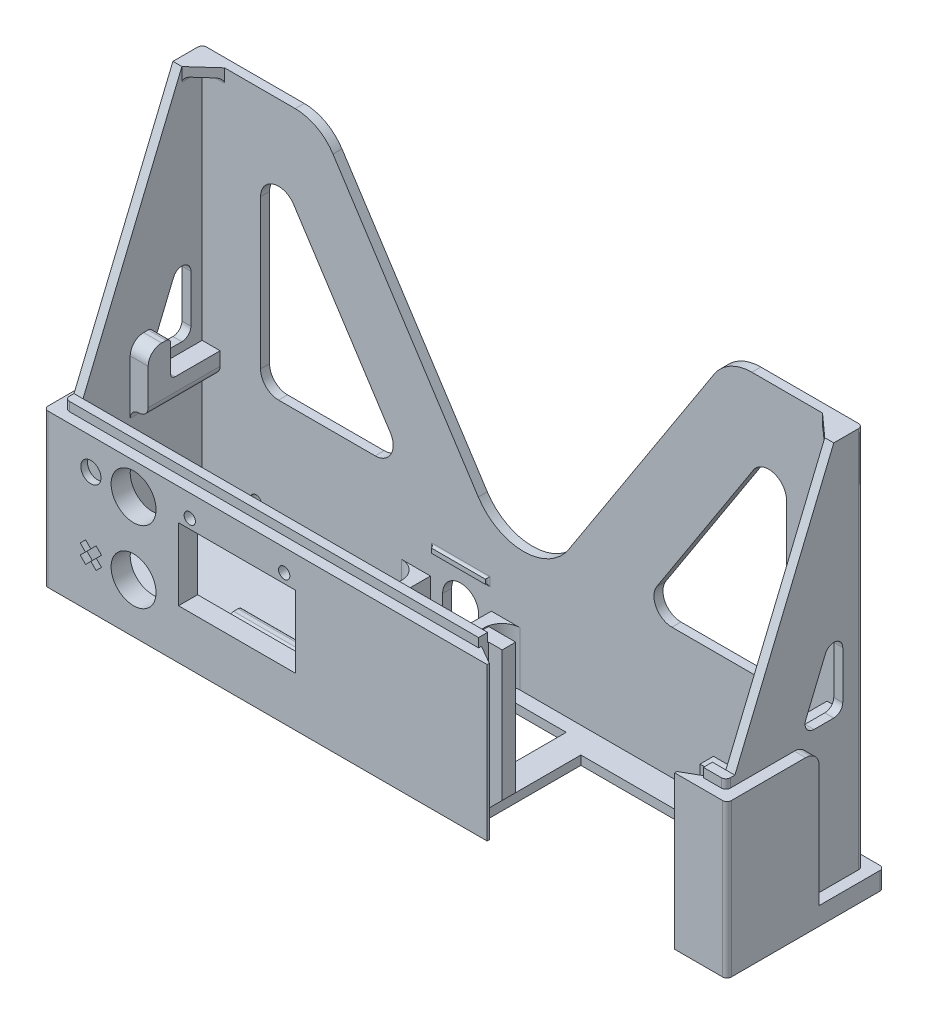
SolidWorks part; units mm, degrees
ref_plane "Plano frontal" through (0, 0, 0) normal (0, 0, 1) x (1, 0, 0)
ref_plane "Plano superior" through (0, 0, 0) normal (0, 1, 0) x (1, 0, 0)
ref_plane "Plano direito" through (0, 0, 0) normal (1, 0, 0) x (0, 0, -1)
sketch "Esboço1" plane through (0, 0, 0) normal (0, 1, 0) x (1, 0, 0)
  line L1 (0, 0) -> (152, 0)
  line L2 (0, 0) -> (0, 35)
  line L3 (0, 35) -> (152, 35)
  line L4 (152, 0) -> (152, 35)
extrude "Ressalto-extrusão1" add sketch "Esboço1" along normal blind 2
sketch "Esboço3" plane through (0, 2, 0) normal (0, 1, 0) x (1, 0, 0)
  line L0 (4, 31) -> (4, 4)
  line L1 (4, 4) -> (148, 4)
  line L2 (148, 4) -> (148, 31)
  line L3 (148, 31) -> (4, 31)
  line L8 (0, 35) -> (0, 0)
  line L9 (0, 0) -> (152, 0)
  line L10 (152, 0) -> (152, 35)
  line L11 (152, 35) -> (0, 35)
  line L12 (0, 35) -> (0, 0)
  line L13 (0, 0) -> (152, 0)
  line L14 (152, 0) -> (152, 35)
  line L15 (152, 35) -> (0, 35)
  dimension "D1" = 0
  dimension "D2" = 4
extrude "Ressalto-extrusão2" add sketch "Esboço3" along normal blind 32
sketch "Esboço5" plane through (0, 34, 0) normal (0, 1, 0) x (1, 0, 0)
  line L0 (152, 0) -> (152, 35) construction
  line L1 (0, 35) -> (152, 35)
  line L2 (0, 35) -> (0, 20.5)
  line L3 (0, 20.5) -> (152, 20.5)
  line L4 (152, 35) -> (152, 20.5)
  dimension "D1" = 14.5
extrude "Corte-extrusão1" cut sketch "Esboço5" against normal blind 30
fillet "Filete2" radius 3 2 edges at (2, 34, -20.5) (150, 34, -20.5)
sketch "Esboço6" plane through (0, 2, 0) normal (0, 1, 0) x (1, 0, 0)
  line L0 (152, 35) -> (0, 0) construction
  line L1 (0, 35) -> (152, 0) construction
  line L3 (149.5, 2.25) -> (2.5, 2.25)
  line L4 (149.5, 2.25) -> (149.5, 32.75)
  line L5 (149.5, 32.75) -> (2.5, 32.75)
  line L6 (2.5, 2.25) -> (2.5, 32.75)
  line L7 (149.5, 2.25) -> (2.5, 32.75) construction
  line L8 (149.5, 32.75) -> (2.5, 2.25) construction
  line L13 (147.5, 4.25) -> (4.5, 4.25)
  line L14 (4.5, 4.25) -> (4.5, 30.75)
  line L15 (147.5, 30.75) -> (4.5, 30.75)
  line L16 (147.5, 4.25) -> (147.5, 30.75)
  point P8 (76, 17.5)
  dimension "D1" = 147
  dimension "D2" = 30.5
  dimension "D3" = 2
extrude "Ressalto-extrusão3" add sketch "Esboço6" along normal offset from surface (87 mm away) 55 up to face at (76, 34, -9.75) offset beyond the face yes
fillet "Filete3" radius 1 8 edges at (2.5, 61.5, -2.25) (149.5, 61.5, -2.25) (149.5, 46.5, -32.75) (152, 2, -35) (0, 2, -35) (2.5, 46.5, -32.75) (152, 17, 0) (0, 17, 0)
sketch "Esboço7" plane through (0, 0, 0) normal (0, 0, 1) x (1, 0, 0)
  line L0 (1, 34) -> (151, 34) construction
  line L1 (30, 27) -> (56, 27)
  line L2 (30, 27) -> (30, 11)
  line L3 (30, 11) -> (56, 11)
  line L4 (56, 27) -> (56, 11)
  line L5 (32.5, 29.1) -> (53.5, 29.1) construction
  line L6 (30, 27) -> (20, 27) construction
  line L7 (20, 27) -> (20, 11) construction
  line L9 (0, 4) -> (0, 31) construction
  circle A0 centre (20, 27) radius 5
  circle A1 centre (20, 11) radius 5
  circle A2 centre (32.5, 29.1) radius 1.25
  circle A3 centre (53.5, 29.1) radius 1.25
  dimension "D5" = 10
  dimension "D6" = 10
  dimension "D7" = 20
  dimension "D8" = 2.5
  dimension "D12" = 2.5
  dimension "D13" = 2.5
  dimension "D1" = 16
  dimension "D2" = 26
  dimension "D3" = 7
  dimension "D4" = 10
  dimension "D9" = 2.1
  dimension "D10" = 16
  dimension "D11" = 2.5
extrude "Corte-extrusão2" cut sketch "Esboço7" against normal up to surface (4.25 mm away) up to face at (76, 45.5, -4.25)
sketch "Esboço8" plane through (0, 0, 0) normal (0, 0, 1) x (1, 0, 0)
  line L0 (15, 11) -> (10.5, 11) construction
  line L1 (9.3333, 13.3688) -> (10.5, 12.2021)
  line L2 (8, 8.5) -> (13, 8.5) construction
  line L3 (8, 8.5) -> (8, 13.5) construction
  line L4 (8, 13.5) -> (13, 13.5) construction
  line L5 (13, 8.5) -> (13, 13.5) construction
  line L6 (8, 8.5) -> (13, 13.5) construction
  line L7 (8, 13.5) -> (13, 8.5) construction
  line L8 (9.3333, 13.3688) -> (8.1312, 12.1667)
  line L9 (12.8688, 9.8333) -> (11.6667, 8.6312)
  line L10 (8.1312, 12.1667) -> (9.2979, 11)
  line L11 (9.3333, 13.3688) -> (11.6667, 8.6312) construction
  line L12 (12.8688, 9.8333) -> (8.1312, 12.1667) construction
  line L13 (12.8688, 12.1667) -> (11.7021, 11)
  line L14 (12.8688, 12.1667) -> (11.6667, 13.3688)
  line L15 (9.3333, 8.6312) -> (8.1312, 9.8333)
  line L16 (11.6667, 13.3688) -> (10.5, 12.2021)
  line L17 (12.8688, 12.1667) -> (8.1312, 9.8333) construction
  line L18 (9.3333, 8.6312) -> (11.6667, 13.3688) construction
  line L19 (10.5, 9.7979) -> (11.6667, 8.6312)
  line L20 (10.5, 9.7979) -> (9.3333, 8.6312)
  line L21 (11.7021, 11) -> (12.8688, 9.8333)
  line L22 (9.2979, 11) -> (8.1312, 9.8333)
  line L23 (15, 27) -> (10.5, 27) construction
  circle A0 centre (10.5, 11) radius 2.5 construction
  circle A1 centre (20, 11) radius 5 construction
  circle A2 centre (20, 27) radius 5 construction
  circle A3 centre (10.5, 27) radius 2.25
  dimension "D1" = 5
  dimension "D3" = 4.5
  dimension "D2" = 4.5
  dimension "D4" = 4.5
extrude "Corte-extrusão3" cut sketch "Esboço8" against normal blind 1.5
sketch "Esboço10" plane through (0, 0, 0) normal (0, -1, 0) x (1, 0, 0)
  line L0 (1, 0) -> (151, 0) construction
  line L1 (139.5, 0) -> (99.5, 0)
  line L2 (144.5, -2.8868) -> (144.5, -25)
  line L3 (144.5, -25) -> (94.5, -25)
  line L4 (94.5, -2.8868) -> (94.5, -25)
  line L5 (151, -35) -> (1, -35) construction
  line L6 (147.5, -4.25) -> (147.5, -30.75) construction
  line L7 (98.634, -0.5) -> (94.5, -2.8868)
  line L8 (144.5, -2.8868) -> (140.366, -0.5)
  line L9 (99.5, 0) -> (98.634, 0)
  line L10 (98.634, 0) -> (98.634, -0.5)
  line L11 (139.5, 0) -> (140.366, 0)
  line L12 (140.366, 0) -> (140.366, -0.5)
  line L13 (99.5, 0) -> (98.634, -0.5) construction
  line L14 (140.366, -0.5) -> (139.5, 0) construction
  point P0 (144.5, 0)
  point P3 (94.5, 0)
  dimension "D1" = 10
  dimension "D2" = 3
  dimension "D3" = 50
  dimension "D4" = 5
  dimension "D5" = 30
  dimension "D6" = 5
  dimension "D7" = 30
  dimension "D8" = 0.5
  dimension "D9" = 0.5
extrude "Corte-extrusão5" cut sketch "Esboço10" against normal up to surface (89 mm away)
sketch "Esboço11" plane through (0, 89, 0) normal (0, 1, 0) x (1, 0, 0)
  line L0 (94.5, 2.8868) -> (94.5, 2.25)
  line L1 (3.5, 2.25) -> (95.6029, 2.25) construction
  line L2 (94.5, 2.25) -> (95.6029, 2.25)
  line L3 (95.6029, 2.25) -> (94.5, 2.8868)
  line L4 (143.3971, 2.25) -> (144.5, 2.8868)
  line L5 (144.5, 2.8868) -> (144.5, 2.25)
  line L6 (143.3971, 2.25) -> (148.5, 2.25) construction
  line L7 (144.5, 2.25) -> (143.3971, 2.25)
extrude "Corte-extrusão6" cut sketch "Esboço11" against normal up to surface (55 mm away) up to face at (147.4493, 34, -4.8706)
sketch "Esboço12" plane through (0, 0, 0) normal (0, -1, 0) x (1, 0, 0)
  line L0 (94.5, -2.8868) -> (94.5, -25) construction
  line L1 (74.5, -8.25) -> (88.5, -8.25)
  line L2 (74.5, -8.25) -> (74.5, -27.75)
  line L3 (74.5, -27.75) -> (88.5, -27.75)
  line L4 (88.5, -8.25) -> (88.5, -27.75)
  line L6 (56, -12.25) -> (68, -17.25) construction
  line L8 (56, -17.25) -> (56, -12.25)
  line L10 (68, -17.25) -> (68, -12.25)
  line L11 (68, -12.25) -> (56, -17.25) construction
  line L12 (62, -14.75) -> (74.5, -14.75) construction
  line L13 (4.5, -4.25) -> (94.5, -4.25) construction
  line L14 (74.5, -8.25) -> (62, -8.25) construction
  line L32 (62, -14.75) -> (62, -32) construction
  line L33 (151, -35) -> (1, -35) construction
  line L35 (58, -29) -> (66, -29)
  line L36 (58, -29) -> (58, -35)
  line L37 (58, -35) -> (66, -35)
  line L38 (66, -29) -> (66, -35)
  line L39 (58, -29) -> (66, -35) construction
  line L40 (58, -35) -> (66, -29) construction
  arc A0 (56, -17.25) -> (68, -17.25) centre (62, -14.75) ccw
  arc A1 (68, -12.25) -> (56, -12.25) centre (62, -14.75) ccw
  circle A2 centre (62, -14.75) radius 6.5 construction
  dimension "D4" = 6.5
  dimension "D6" = 12.5
  dimension "D1" = 14
  dimension "D2" = 19.5
  dimension "D3" = 6
  dimension "D5" = 12
  dimension "D7" = 4
  dimension "D11" = 6
  dimension "D17" = 8
extrude "Corte-extrusão7" cut sketch "Esboço12" against normal blind 16
fillet "Filete4" radius 4 4 edges at (62, 16, -30.75) (66, 16, -31.75) (58, 16, -31.75) (62, 16, -32.75)
sketch "Esboço15" plane through (0, 2, 0) normal (0, 1, 0) x (1, 0, 0)
  line L0 (68.6192, 22.35) -> (67.1192, 23.85)
  line L1 (68.8233, 24.75) -> (67.1192, 24.75)
  line L2 (68.8233, 24.75) -> (68.8233, 30.75)
  line L4 (55.2871, 24.75) -> (55.2871, 30.75)
  line L5 (68.8233, 24.75) -> (55.2871, 30.75) construction
  line L6 (68.8233, 30.75) -> (55.2871, 24.75) construction
  line L7 (147.5, 30.75) -> (4.5, 30.75) construction
  line L8 (52.8871, 22.35) -> (52.8871, 26.75)
  line L9 (71.2233, 22.35) -> (68.6192, 22.35)
  line L10 (71.2233, 22.35) -> (71.2233, 26.75)
  line L11 (56.9912, 24.75) -> (55.2871, 24.75)
  line L12 (55.4912, 22.35) -> (52.8871, 22.35)
  line L14 (67.1192, 24.75) -> (67.1192, 23.85)
  line L16 (56.9912, 24.75) -> (56.9912, 23.85)
  line L17 (68.8233, 24.75) -> (55.2871, 24.75) construction
  line L18 (71.2233, 30.75) -> (68.8233, 30.75)
  line L19 (71.2233, 22.35) -> (52.8871, 22.35) construction
  line L20 (55.2871, 30.75) -> (52.8871, 30.75)
  line L21 (56.9912, 23.85) -> (55.4912, 22.35)
  line L22 (52.8871, 30.75) -> (48.8871, 30.75)
  line L24 (71.2233, 22.35) -> (71.2233, 30.75) construction
  line L25 (71.2233, 30.75) -> (75.2233, 30.75)
  line L27 (52.8871, 22.35) -> (52.8871, 30.75) construction
  arc A0 (71.2233, 26.75) -> (75.2233, 30.75) centre (75.2233, 26.75) cw
  arc A1 (48.8871, 30.75) -> (52.8871, 26.75) centre (48.8871, 26.75) cw
  point P0 (62.0552, 27.75)
  point P13 (62.0552, 23.55)
  point P14 (56.9912, 22.35)
  point P16 (67.1192, 22.35)
  dimension "D3" = 1.5
  dimension "D6" = 4
  dimension "D7" = 4
  dimension "D1" = 1.5
  dimension "D2" = 2.4
  dimension "D4" = 1.5
  dimension "D5" = 1.5
extrude "Ressalto-extrusão4" add sketch "Esboço15" along normal blind 12
sketch "Esboço16" plane through (0, 0, -30.75) normal (0, 0, 1) x (1, 0, 0)
  line L0 (62, 2) -> (62, 19.5) construction
  line L1 (66, 2) -> (58, 2) construction
  line L3 (68, 20) -> (56, 20)
  line L4 (68, 20) -> (68, 19)
  line L5 (68, 19) -> (56, 19)
  line L6 (56, 20) -> (56, 19)
  line L7 (68, 20) -> (56, 19) construction
  line L8 (68, 19) -> (56, 20) construction
  dimension "D1" = 17
  dimension "D2" = 1
  dimension "D3" = 12
extrude "Ressalto-extrusão5" add sketch "Esboço16" along normal blind 0.5
fillet "Filete7" radius 0.5 4 edges at (56, 19.5, -30.75) (68, 19.5, -30.75) (62, 20, -30.75) (62, 19, -30.75)
sketch "Esboço18" plane through (30, 0, 0) normal (1, 0, 0) x (0, 0, -1)
  line L0 (4.25, 3.8) -> (7.25, 3.8)
  line L1 (4.25, 89) -> (4.25, 2) construction
  line L2 (8.25, 4.8) -> (8.25, 5.8)
  line L3 (9.25, 6.8) -> (10.25, 6.8)
  line L9 (11.25, 5.8) -> (11.25, 2)
  line L10 (30.75, 2) -> (4.25, 2) construction
  line L11 (11.25, 2) -> (4.25, 2)
  line L12 (4.25, 2) -> (4.25, 3.8)
  arc A1 (8.25, 4.8) -> (7.25, 3.8) centre (7.25, 4.8) cw
  arc A2 (11.25, 5.8) -> (10.25, 6.8) centre (10.25, 5.8) ccw
  arc A3 (9.25, 6.8) -> (8.25, 5.8) centre (9.25, 5.8) ccw
  point P14 (11.25, 6.8)
  point P18 (8.25, 6.8)
  dimension "D2" = 1
  dimension "D3" = 1
  dimension "D6" = 1
  dimension "D1" = 3
  dimension "D4" = 3
  dimension "D5" = 3
extrude "Ressalto-extrusão6" add sketch "Esboço18" along normal blind 18 and the other way blind 1 from offset 4
sketch "Esboço20" plane through (147.5, 0, 0) normal (-1, 0, 0) x (0, 0, 1)
  line L3 (-2.25, 89) -> (-2.25, 36)
  line L11 (-31.75, 4) -> (-31.75, 89) construction
  line L12 (-2.25, 34) -> (-2.25, 89) construction
  line L13 (-2.25, 36) -> (-4.25, 36)
  line L15 (-2.25, 89) -> (-26.25, 89)
  line L16 (-3.25, 89) -> (-31.75, 89) construction
  line L17 (-26.25, 89) -> (-4.25, 36)
  line L18 (-28.25, 48.5699) -> (-28.25, 38)
  line L19 (-26.25, 36) -> (-21.8625, 36)
  line L20 (-24.4028, 49.3366) -> (-20.0153, 38.7668)
  line L21 (-38.7185, 83.8244) -> (-16.7185, 30.8244) construction
  line L22 (-2.25, 34) -> (-2.25, 89) construction
  line L23 (-4.25, 89) -> (-30.75, 89) construction
  line L24 (-17.5, 34) -> (-3.25, 34) construction
  arc A0 (-28.25, 48.5699) -> (-24.4028, 49.3366) centre (-26.25, 48.5699) cw
  arc A1 (-28.25, 38) -> (-26.25, 36) centre (-26.25, 38) ccw
  arc A2 (-20.0153, 38.7668) -> (-21.8625, 36) centre (-21.8625, 38) cw
  dimension "D2" = 2
  dimension "D1" = 13.5
  dimension "D3" = 24
  dimension "D4" = 2
  dimension "D5" = 3.5
  dimension "D6" = 2
extrude "Corte-extrusão9" cut sketch "Esboço20" against normal through all both and the other way through all
sketch "Esboço22" plane through (0, 0, -30.75) normal (0, 0, 1) x (1, 0, 0)
  line L0 (147.5, 89) -> (4.5, 89) construction
  line L1 (121.3441, 89) -> (30.6559, 89)
  line L2 (134.5, 68.1869) -> (134.5, 35)
  line L3 (130.5, 31) -> (109.0024, 31)
  line L4 (17.5, 68.1869) -> (17.5, 35)
  line L5 (147.5, 89) -> (147.5, 2) construction
  line L6 (4.5, 89) -> (4.5, 2) construction
  line L7 (94.5, 36) -> (3.5, 36) construction
  line L8 (86.0716, 34.548) -> (121.3441, 89)
  line L9 (65.9284, 34.548) -> (30.6559, 89)
  line L10 (121.3441, 89) -> (30.6559, 89)
  line L11 (46.3548, 37.1747) -> (24.8572, 70.3616)
  line L12 (105.6452, 37.1747) -> (127.1428, 70.3616)
  line L13 (48.8871, 2) -> (4.5, 2) construction
  line L14 (147.5, 2) -> (75.2233, 2) construction
  line L15 (42.9976, 31) -> (21.5, 31)
  arc A0 (65.9284, 34.548) -> (86.0716, 34.548) centre (76, 41.0721) ccw
  arc A1 (24.8572, 70.3616) -> (17.5, 68.1869) centre (21.5, 68.1869) ccw
  arc A2 (17.5, 35) -> (21.5, 31) centre (21.5, 35) ccw
  arc A3 (42.9976, 31) -> (46.3548, 37.1747) centre (42.9976, 35) ccw
  arc A4 (109.0024, 31) -> (105.6452, 37.1747) centre (109.0024, 35) cw
  arc A5 (134.5, 35) -> (130.5, 31) centre (130.5, 35) cw
  arc A6 (127.1428, 70.3616) -> (134.5, 68.1869) centre (130.5, 68.1869) cw
  circle A7 centre (16.5, 9) radius 1.25
  circle A8 centre (135.5, 9) radius 1.25
  point P19 (76, 19)
  point P34 (50.3546, 31)
  line M24 (147.5, 89) -> (4.5, 89)
  dimension "D4" = 12
  dimension "D7" = 4
  dimension "D9" = 7
  dimension "D6" = 7
  dimension "D11" = 2.5
  dimension "D12" = 2.5
  dimension "D1" = 13
  dimension "D2" = 13
  dimension "D3" = 5
  dimension "D8" = 12
  dimension "D5" = 15
  dimension "D10" = 12
extrude "Corte-extrusão10" cut sketch "Esboço22" against normal through all contours L9 A0 L8 M24 | A6 L12 A4 L3 A5 L2 | L15 A3 L11 A1 L4 A2 | A7 | A8
sketch "Esboço25" plane through (0, 89, 0) normal (0, 1, 0) x (1, 0, 0)
  line L0 (147.5, 30.75) -> (142.5, 30.75)
  line L1 (147.5, 30.75) -> (121.3441, 30.75) construction
  line L2 (142.5, 30.75) -> (147.5, 26.25)
  line L3 (147.5, 26.25) -> (147.5, 30.75)
  line L4 (4.5, 30.75) -> (9.5, 30.75)
  line L5 (30.6559, 30.75) -> (4.5, 30.75) construction
  line L6 (9.5, 30.75) -> (4.5, 26.25)
  line L7 (4.5, 26.25) -> (4.5, 30.75)
extrude "Ressalto-extrusão8" add sketch "Esboço25" against normal blind 2
fillet "Filete8" radius 1 4 edges at (4.5, 87, -28.5) (7, 87, -30.75) (147.5, 87, -28.5) (145, 87, -30.75)
sketch "Esboço26" plane through (147.5, 0, 0) normal (-1, 0, 0) x (0, 0, 1)
  line L1 (-30.75, 34) -> (-20.75, 34)
  line L5 (-1, 34) -> (-17.5, 34) construction
  line L7 (-19.75, 35) -> (-19.75, 41)
  line L8 (-18.75, 42) -> (-17.75, 42)
  line L15 (-14.75, 39) -> (-14.75, 29)
  line L16 (-14.75, 29) -> (-30.75, 29)
  line L17 (-30.75, 29) -> (-30.75, 34)
  arc A2 (-18.75, 42) -> (-19.75, 41) centre (-18.75, 41) ccw
  arc A3 (-14.75, 39) -> (-17.75, 42) centre (-17.75, 39) ccw
  arc A4 (-20.75, 34) -> (-19.75, 35) centre (-20.75, 35) ccw
  point P22 (-19.75, 34)
  dimension "D4" = 1
  dimension "D5" = 3
  dimension "D6" = 1
  dimension "D1" = 11
extrude "Ressalto-extrusão9" add sketch "Esboço26" along normal blind 4
fillet "Filete10" radius 2 2 edges at (143.5, 29, -22.75) (147.5, 29, -22.75)
sketch "Esboço27" plane through (4.5, 0, -4.5) normal (-1, 0, 0) x (0, 0, 1)
  line L0 (-10.25, 39) -> (-10.25, 27) construction
  line L1 (-26.25, 34) -> (-16.25, 34)
  line L6 (-26.25, 34) -> (-16.25, 34) construction
  line L7 (-15.25, 35) -> (-15.25, 41)
  line L8 (-14.25, 42) -> (-13.25, 42)
  line L15 (-10.25, 39) -> (-10.25, 29)
  line L16 (-10.25, 29) -> (-26.25, 29)
  line L17 (-26.25, 29) -> (-26.25, 34)
  arc A2 (-14.25, 42) -> (-15.25, 41) centre (-14.25, 41) ccw
  arc A3 (-10.25, 39) -> (-13.25, 42) centre (-13.25, 39) ccw
  arc A4 (-16.25, 34) -> (-15.25, 35) centre (-16.25, 35) ccw
  point P22 (-15.25, 34)
  dimension "D4" = 1
  dimension "D5" = 3
  dimension "D6" = 1
  dimension "D1" = 11
extrude "Ressalto-extrusão10" add sketch "Esboço27" against normal blind 4
fillet "Filete11" radius 2 2 edges at (8.5, 29, -22.75) (4.5, 29, -22.75)
fillet "Filete12" radius 10 2 edges at (30.6559, 89, -31.75) (121.3441, 89, -31.75)
sketch "Esboço29" plane through (0, 2, 0) normal (0, 1, 0) x (1, 0, 0)
  line L0 (94.5, 4.25) -> (94.5, 4.5)
  line L1 (94.5, 4.25) -> (94.5, 25) construction
  line L2 (94.5, 4.5) -> (97.5, 4.5)
  line L3 (97.5, 4.5) -> (97.5, 7.5)
  line L4 (97.5, 7.5) -> (91.5, 7.5)
  line L5 (91.5, 7.5) -> (91.5, 4.25)
  line L6 (52, 4.25) -> (94.5, 4.25) construction
  line L7 (91.5, 4.25) -> (94.5, 4.25)
  line L8 (1, 0) -> (98.634, 0) construction
  line L9 (147.5, 4.25) -> (147.5, 7.5)
  line L10 (147.5, 4.25) -> (147.5, 30.75) construction
  line L11 (147.5, 7.5) -> (141.5, 7.5)
  line L12 (141.5, 7.5) -> (141.5, 4.5)
  line L13 (141.5, 4.5) -> (144.5, 4.5)
  line L14 (144.5, 25) -> (144.5, 4.25) construction
  line L15 (144.5, 4.5) -> (144.5, 4.25)
  line L16 (144.5, 4.25) -> (147.5, 4.25)
  line L17 (140.366, 0) -> (151, 0) construction
  dimension "D1" = 3
  dimension "D2" = 3
  dimension "D3" = 3
  dimension "D4" = 4.5
  dimension "D5" = 4.5
  dimension "D6" = 3
  dimension "D7" = 3
extrude "Ressalto-extrusão11" add sketch "Esboço29" along normal up to surface (32 mm away) up to face at (147.2646, 34, -4.6723)
chamfer "Chanfro1" distance 3 angle 45 2 edges at (97.5, 2, -6) (141.5, 2, -6)
fillet "Filete13" radius 1 1 edges at (91.5, 18, -4.25)
fillet "Filete14" radius 1 1 edges at (147.5, 18, -7.5)
sketch "Esboço4" plane through (0, 34, 0) normal (0, 1, 0) x (1, 0, 0)
